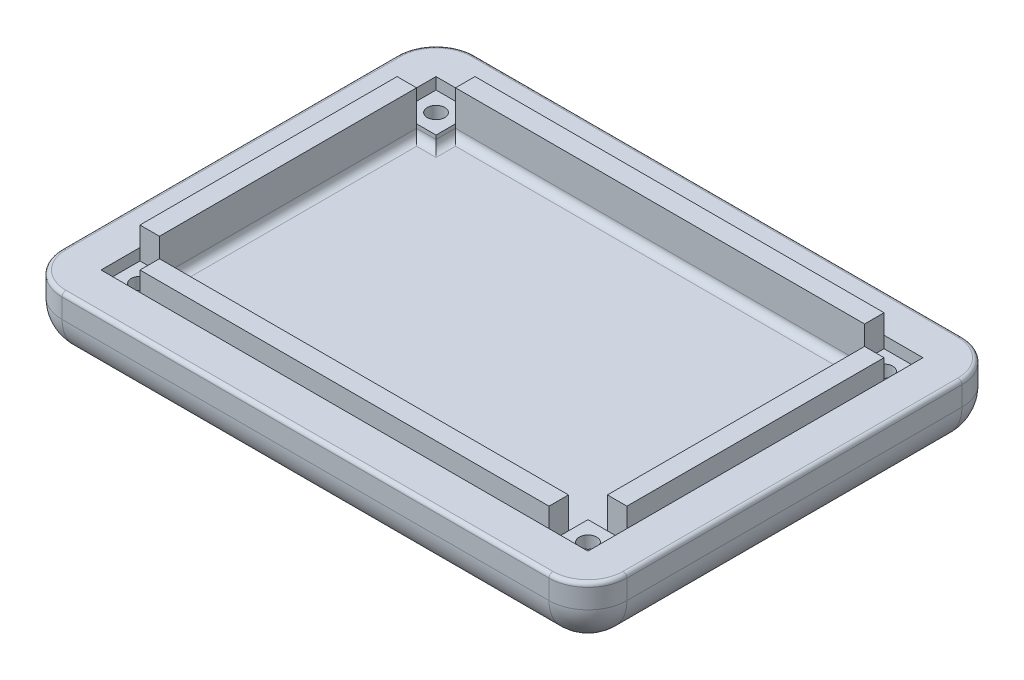
SolidWorks part; units mm, degrees
ref_plane "Front Plane" through (0, 0, 0) normal (0, 0, 1) x (1, 0, 0)
ref_plane "Top Plane" through (0, 0, 0) normal (0, 1, 0) x (1, 0, 0)
ref_plane "Right Plane" through (0, 0, 0) normal (1, 0, 0) x (0, 0, -1)
sketch "Sketch1" plane through (0, 0, 0) normal (0, 1, 0) x (1, 0, 0)
  line L0 (62.5, -43) -> (62.5, 43)
  line L1 (72.5, -53) -> (-72.5, -53)
  line L2 (72.5, -53) -> (72.5, 53)
  line L3 (72.5, 53) -> (-72.5, 53)
  line L4 (-72.5, -53) -> (-72.5, 53)
  line L5 (0, 53) -> (0, -53) construction
  line L6 (72.5, 0) -> (-72.5, 0) construction
  line L7 (62.5, 43) -> (-62.5, 43)
  line L8 (-62.5, -43) -> (-62.5, 43)
  line L9 (62.5, -43) -> (-62.5, -43)
  point P0 (0, 0)
  dimension "D1" = 145
  dimension "D2" = 106
  dimension "D3" = 10
extrude "Boss-Extrude1" add sketch "Sketch1" along normal blind 16 contours L9 L0 L7 L8 | L0 L9 L8 L7 | L4 L1 L2 L3 region at (0, 0, 0) region at (0, 0, 51.2039)
extrude "Cut-Extrude1" cut sketch "Sketch1<4>" against normal offset from surface (6 mm away) 10 from surface contours L8 L7 L0 L9 up to face at (0, 0, 0) starting at face at (0, 16, 0)
sketch "Sketch1<4>" plane through (0, 0, 0) normal (0, 1, 0) x (1, 0, 0) same geometry as "Sketch1"
sketch "Sketch6" plane through (0, 10, 0) normal (0, 1, 0) x (1, 0, 0)
  line L0 (-62.5, 43) -> (-62.5, -43) construction
  line L1 (-62.5, 43) -> (-52.5, 43)
  line L2 (-62.5, 43) -> (-62.5, 33)
  line L3 (-62.5, 33) -> (-52.5, 33)
  line L4 (-52.5, 43) -> (-52.5, 33)
  line L5 (-62.5, 43) -> (62.5, 43) construction
  point P8 (-57.5, 38)
  dimension "D1" = 10
extrude "Boss-Extrude5" add sketch "Sketch6" along normal blind 3
hole_wizard "M4 Clearance Hole1" positions "Sketch7" profile "Sketch8" hole size "M4" standard "ANSI Metric"
sketch "Sketch7" plane through (0, 13, 0) normal (0, 1, 0) x (1, 0, 0)
  point P0 (-57.5, 38)
sketch "Sketch8" plane through (-57.5, 13, -38) normal (1, 0, 0) x (0, 0, 1)
  line L0 (0, 0) -> (0, 7.25)
  line L1 (0, 7.25) -> (2.25, 5)
  line L2 (2.25, 5) -> (2.25, 0)
  line L5 (2.25, 0) -> (0, 0)
  line L10 (0, 7.25) -> (-2.25, 5) construction
  line L11 (0, -6.35) -> (0, 107.95) construction
  dimension "Hole Dia." = 4.5
  dimension "Hole Depth" = 5
  dimension "Drill Angle" = 90
mirror "Mirror1" about plane through (0, 0, 0) normal (1, 0, 0) of "M4 Clearance Hole1", "Boss-Extrude5"
mirror "Mirror2" about plane through (0, 0, 0) normal (0, 0, 1) of "Mirror1"
sketch "Sketch4" plane through (0, 0, 0) normal (0, 0, 1) x (1, 0, 0)
  line L5 (52.5, 10) -> (-52.5, 10) construction
  line L7 (-57.5, 10) -> (-57.5, 21)
  line L8 (-57.5, 21) -> (-62.5, 21)
  line L10 (-62.5, 13) -> (-62.5, 16) construction
  line L11 (-62.5, 10) -> (-62.5, 16)
  line L12 (-62.5, 10) -> (-57.5, 10)
  line L13 (-62.5, 21) -> (-62.5, 16)
  line L14 (72.5, 16) -> (-72.5, 16) construction
  line L15 (-62.5, 10) -> (-52.5, 10) construction
  point P2 (-62.5, 10)
  point P5 (0, 0)
  dimension "D1" = 5
  dimension "D4" = 5
extrude "Boss-Extrude6" add sketch "Sketch4" against normal up to surface and the other way up to surface up to face at (-57.5, 11.5, -33) other way up to face at (-57.5, 11.5, 33)
sketch "Sketch9" plane through (0, 0, 0) normal (1, 0, 0) x (0, 0, -1)
  line L0 (-53, 16) -> (53, 16) construction
  line L1 (-43, 10) -> (-38, 10)
  line L2 (-43, 10) -> (-43, 21)
  line L3 (-43, 21) -> (-38, 21)
  line L4 (-38, 10) -> (-38, 21)
  dimension "D1" = 5
  dimension "D2" = 5
extrude "Boss-Extrude7" add sketch "Sketch9" along normal up to surface and the other way up to surface contours L3 L4 L1 L2 up to face at (52.5, 11.5, 38) other way up to face at (-52.5, 11.5, 38)
mirror "Mirror3" about plane through (0, 0, 0) normal (1, 0, 0) of "Boss-Extrude6"
mirror "Mirror4" about plane through (0, 0, 0) normal (0, 0, 1) of "Boss-Extrude7"
fillet "Fillet1" radius 10 8 edges at (0, 0, 53) (72.5, 0, 0) (0, 0, -53) (-72.5, 0, 0) (-72.5, 8, -53) (72.5, 8, -53) (72.5, 8, 53) (-72.5, 8, 53)
fillet "Fillet3" radius 2 12 edges at (52.5, 10, -35.5) (55, 10, -33) (57.5, 10, 0) (55, 10, 33) (52.5, 10, 35.5) (0, 10, 38) (-52.5, 10, 35.5) (-55, 10, 33) (-57.5, 10, 0) (-55, 10, -33) (-52.5, 10, -35.5) (0, 10, -38)
fillet "Fillet11" radius 1 8 edges at (-69.5711, 16, 50.0711) (0, 16, 53) (69.5711, 16, 50.0711) (72.5, 16, 0) (69.5711, 16, -50.0711) (0, 16, -53) (-69.5711, 16, -50.0711) (-72.5, 16, 0)
equation "\"wall_thickness\"= 5mm"
